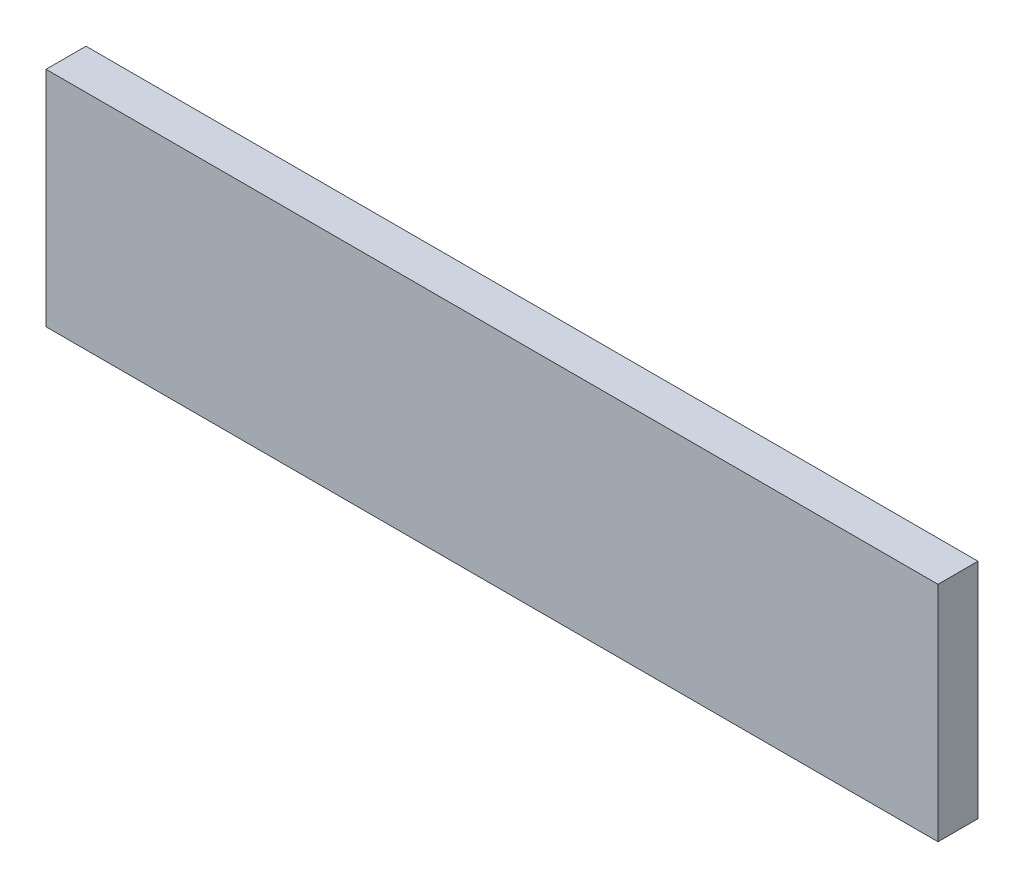
SolidWorks part; units mm, degrees
material "NEOPRENE"
ref_plane "Front Plane" through (0, 0, 0) normal (0, 0, 1) x (1, 0, 0)
ref_plane "Top Plane" through (0, 0, 0) normal (0, 1, 0) x (1, 0, 0)
ref_plane "Right Plane" through (0, 0, 0) normal (1, 0, 0) x (0, 0, -1)
ref_axis "Axis1" through (0, 0, 0) along (0, 1, 0)
sketch "Sketch3" plane through (0, 0, 0) normal (0, 0, 1) x (1, 0, 0)
  line L1 (-34, -8.5) -> (34, -8.5)
  line L2 (-34, -8.5) -> (-34, 8.5)
  line L3 (-34, 8.5) -> (34, 8.5)
  line L4 (34, -8.5) -> (34, 8.5)
  line L5 (-34, -8.5) -> (34, 8.5) construction
  line L6 (-34, 8.5) -> (34, -8.5) construction
  point P0 (0, 0)
  dimension "D1" = 68
  dimension "D2" = 17
extrude "Boss-Extrude1" add sketch "Sketch3" along normal blind 3.048
